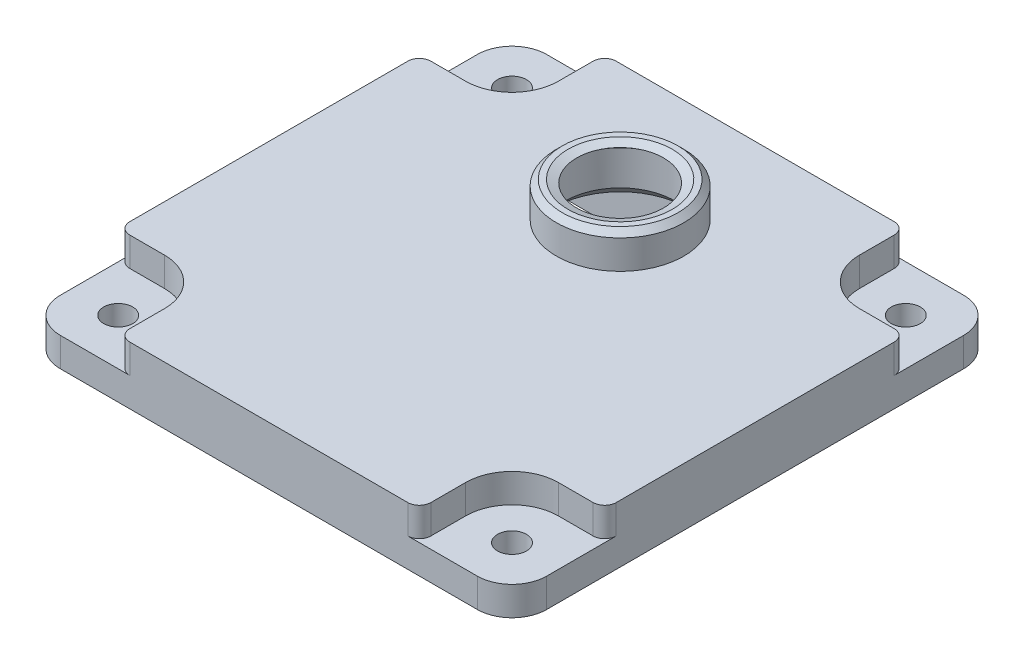
SolidWorks part; units mm, degrees
ref_plane "Front Plane" through (0, 0, 0) normal (0, 0, 1) x (1, 0, 0)
ref_plane "Top Plane" through (0, 0, 0) normal (0, 1, 0) x (1, 0, 0)
ref_plane "Right Plane" through (0, 0, 0) normal (1, 0, 0) x (0, 0, -1)
sketch "Sketch2" plane through (0, 0, 0) normal (0, 1, 0) x (1, 0, 0)
  line L1 (-21, 21) -> (21, 21)
  line L2 (-21, 21) -> (-21, -21)
  line L3 (-21, -21) -> (21, -21)
  line L4 (21, 21) -> (21, -21)
  line L5 (-21, 21) -> (21, -21) construction
  line L6 (-21, -21) -> (21, 21) construction
  circle A0 centre (0, 9.3373) radius 4.75
  point P0 (0, 0)
  point P8 (0, 6.2967)
  point P9 (0, 13.6485)
  point P10 (0.4735, 10.1128)
  point P11 (0, 10.3999)
  point P12 (0, 9.3373)
  dimension "D3" = 9.5
  dimension "D1" = 42
  dimension "D2" = 42
extrude "Boss-Extrude1" add sketch "Sketch2" against normal blind 2
ref_plane "Plane1" through (0, 0, -9.3373) normal (0, 0, 1) x (1, 0, 0)
sketch "Sketch3" plane through (0, 0, -9.3373) normal (0, 0, 1) x (1, 0, 0)
  line L1 (-4.75, 0) -> (-5.5, 0)
  line L2 (-5.5, 0) -> (-5.5, 3)
  line L4 (-5.5, 3) -> (-4.5, 3)
  line L8 (-4.75, 2) -> (-4.75, 0)
  line L9 (0, 0) -> (0, 7.3617) construction
  line L10 (-4.75, 2) -> (-3.75, 2.727)
  line L11 (-3.75, 2.727) -> (-4.5, 3)
  line L13 (0, 1.3621) -> (-4.5, 3) construction
  point P6 (-3.4803, 2.1355)
  point P8 (0, 0)
  point P13 (0, 0)
  point P14 (-3.6076, 2.6879)
  point P15 (-3.1722, 2.5167)
  point P16 (-3.7379, 2.7226)
  point P17 (-4.75, 1.7782)
  dimension "D1" = 70
  dimension "D2" = 3
  dimension "D3" = 1
  dimension "D4" = 0.75
  dimension "D5" = 0.75
  dimension "D6" = 2
revolve "Revolve1" add sketch "Sketch3" angle 360 about L9
sketch "Sketch4" plane through (0, -2, 0) normal (0, -1, 0) x (1, 0, 0)
  line L8 (-21, 21) -> (21, 21)
  line L9 (-21, 21) -> (-21, -21)
  line L10 (-21, -21) -> (21, -21)
  line L11 (21, 21) -> (21, -21)
  line L12 (-21, 21) -> (21, -21) construction
  line L13 (-21, -21) -> (21, 21) construction
  line L14 (-17, 11.5228) -> (-17, -11.5228)
  line L15 (-11.5228, -17) -> (11.5228, -17)
  line L16 (17, 11.5228) -> (17, -11.5228)
  line L17 (-11.5228, 17) -> (11.5228, 17)
  arc A12 (-16.5455, -12.0207) -> (-12.0207, -16.5455) centre (-17, -17) cw
  arc A13 (12.0207, -16.5455) -> (16.5455, -12.0207) centre (17, -17) cw
  arc A14 (16.5455, 12.0207) -> (12.0207, 16.5455) centre (17, 17) cw
  arc A15 (-12.0207, 16.5455) -> (-16.5455, 12.0207) centre (-17, 17) cw
  arc A16 (-16.5455, -12.0207) -> (-17, -11.5228) centre (-16.5, -11.5228) cw
  arc A17 (-12.0207, -16.5455) -> (-11.5228, -17) centre (-11.5228, -16.5) ccw
  arc A18 (12.0207, -16.5455) -> (11.5228, -17) centre (11.5228, -16.5) cw
  arc A19 (16.5455, -12.0207) -> (17, -11.5228) centre (16.5, -11.5228) ccw
  arc A20 (16.5455, 12.0207) -> (17, 11.5228) centre (16.5, 11.5228) cw
  arc A21 (12.0207, 16.5455) -> (11.5228, 17) centre (11.5228, 16.5) ccw
  arc A22 (-12.0207, 16.5455) -> (-11.5228, 17) centre (-11.5228, 16.5) cw
  arc A23 (-16.5455, 12.0207) -> (-17, 11.5228) centre (-16.5, 11.5228) ccw
  point P32 (0, 0)
  point P33 (0, 0)
extrude "Boss-Extrude2" add sketch "Sketch4" along normal blind 3
sketch "Sketch6" plane through (0, -2, 0) normal (0, -1, 0) x (1, 0, 0)
  line L8 (-16.5, 11.5228) -> (-16.5, -11.5228)
  line L9 (-11.5228, -16.5) -> (11.5228, -16.5)
  line L10 (16.5, -11.5228) -> (16.5, 11.5228)
  line L11 (11.5228, 16.5) -> (-11.5228, 16.5)
  line L12 (-16.5, 11.5228) -> (-16.5, -11.5228)
  line L13 (-11.5228, -16.5) -> (11.5228, -16.5)
  line L14 (16.5, -11.5228) -> (16.5, 11.5228)
  line L15 (11.5228, 16.5) -> (-11.5228, 16.5)
  line L16 (-17, 11.5228) -> (-17, -11.5228)
  line L17 (-11.5228, -17) -> (11.5228, -17)
  line L18 (17, -11.5228) -> (17, 11.5228)
  line L19 (11.5228, 17) -> (-11.5228, 17)
  line L20 (-17, 11.5228) -> (-17, -11.5228)
  line L21 (-11.5228, -17) -> (11.5228, -17)
  line L22 (17, -11.5228) -> (17, 11.5228)
  line L23 (11.5228, 17) -> (-11.5228, 17)
  arc A24 (-11.5228, -16.5) -> (-16.5, -11.5228) centre (-17, -17) ccw
  arc A25 (16.5, -11.5228) -> (11.5228, -16.5) centre (17, -17) ccw
  arc A26 (11.5228, 16.5) -> (16.5, 11.5228) centre (17, 17) ccw
  arc A27 (-16.5, 11.5228) -> (-11.5228, 16.5) centre (-17, 17) ccw
  arc A28 (-11.5228, -16.5) -> (-16.5, -11.5228) centre (-17, -17) ccw
  arc A29 (16.5, -11.5228) -> (11.5228, -16.5) centre (17, -17) ccw
  arc A30 (11.5228, 16.5) -> (16.5, 11.5228) centre (17, 17) ccw
  arc A31 (-16.5, 11.5228) -> (-11.5228, 16.5) centre (-17, 17) ccw
  arc A32 (-17, -11.5228) -> (-16.5455, -12.0207) centre (-16.5, -11.5228) ccw
  arc A33 (-12.0207, -16.5455) -> (-16.5455, -12.0207) centre (-17, -17) ccw
  arc A34 (-12.0207, -16.5455) -> (-11.5228, -17) centre (-11.5228, -16.5) ccw
  arc A35 (11.5228, -17) -> (12.0207, -16.5455) centre (11.5228, -16.5) ccw
  arc A36 (16.5455, -12.0207) -> (12.0207, -16.5455) centre (17, -17) ccw
  arc A37 (16.5455, -12.0207) -> (17, -11.5228) centre (16.5, -11.5228) ccw
  arc A38 (17, 11.5228) -> (16.5455, 12.0207) centre (16.5, 11.5228) ccw
  arc A39 (12.0207, 16.5455) -> (16.5455, 12.0207) centre (17, 17) ccw
  arc A40 (12.0207, 16.5455) -> (11.5228, 17) centre (11.5228, 16.5) ccw
  arc A41 (-11.5228, 17) -> (-12.0207, 16.5455) centre (-11.5228, 16.5) ccw
  arc A42 (-16.5455, 12.0207) -> (-12.0207, 16.5455) centre (-17, 17) ccw
  arc A43 (-16.5455, 12.0207) -> (-17, 11.5228) centre (-16.5, 11.5228) ccw
  arc A44 (-17, -11.5228) -> (-16.5455, -12.0207) centre (-16.5, -11.5228) ccw
  arc A45 (-12.0207, -16.5455) -> (-16.5455, -12.0207) centre (-17, -17) ccw
  arc A46 (-12.0207, -16.5455) -> (-11.5228, -17) centre (-11.5228, -16.5) ccw
  arc A47 (11.5228, -17) -> (12.0207, -16.5455) centre (11.5228, -16.5) ccw
  arc A48 (16.5455, -12.0207) -> (12.0207, -16.5455) centre (17, -17) ccw
  arc A49 (16.5455, -12.0207) -> (17, -11.5228) centre (16.5, -11.5228) ccw
  arc A50 (17, 11.5228) -> (16.5455, 12.0207) centre (16.5, 11.5228) ccw
  arc A51 (12.0207, 16.5455) -> (16.5455, 12.0207) centre (17, 17) ccw
  arc A52 (12.0207, 16.5455) -> (11.5228, 17) centre (11.5228, 16.5) ccw
  arc A53 (-11.5228, 17) -> (-12.0207, 16.5455) centre (-11.5228, 16.5) ccw
  arc A54 (-16.5455, 12.0207) -> (-12.0207, 16.5455) centre (-17, 17) ccw
  arc A55 (-16.5455, 12.0207) -> (-17, 11.5228) centre (-16.5, 11.5228) ccw
  dimension "D1" = 0.5
  dimension "D2" = 0
extrude "Boss-Extrude3" add sketch "Sketch6" along normal up to surface (3 mm away) up to face at (0, -5, 0)
sketch "Sketch7" plane through (0, -2, 0) normal (0, -1, 0) x (1, 0, 0)
  line L8 (10.6754, 15.5) -> (-10.6754, 15.5)
  line L9 (-15.5, 10.6754) -> (-15.5, -10.6754)
  line L10 (-10.6754, -15.5) -> (10.6754, -15.5)
  line L11 (15.5, -10.6754) -> (15.5, 10.6754)
  line L12 (10.6754, 15.5) -> (-10.6754, 15.5)
  line L13 (-15.5, 10.6754) -> (-15.5, -10.6754)
  line L14 (-10.6754, -15.5) -> (10.6754, -15.5)
  line L15 (15.5, -10.6754) -> (15.5, 10.6754)
  line L16 (11.5228, 16.5) -> (-11.5228, 16.5)
  line L17 (-16.5, 11.5228) -> (-16.5, -11.5228)
  line L18 (-11.5228, -16.5) -> (11.5228, -16.5)
  line L19 (16.5, -11.5228) -> (16.5, 11.5228)
  line L20 (11.5228, 16.5) -> (-11.5228, 16.5)
  line L21 (-16.5, 11.5228) -> (-16.5, -11.5228)
  line L22 (-11.5228, -16.5) -> (11.5228, -16.5)
  line L23 (16.5, -11.5228) -> (16.5, 11.5228)
  arc A8 (10.6754, 15.5) -> (15.5, 10.6754) centre (17, 17) ccw
  arc A9 (-15.5, 10.6754) -> (-10.6754, 15.5) centre (-17, 17) ccw
  arc A10 (-10.6754, -15.5) -> (-15.5, -10.6754) centre (-17, -17) ccw
  arc A11 (15.5, -10.6754) -> (10.6754, -15.5) centre (17, -17) ccw
  arc A12 (10.6754, 15.5) -> (15.5, 10.6754) centre (17, 17) ccw
  arc A13 (-15.5, 10.6754) -> (-10.6754, 15.5) centre (-17, 17) ccw
  arc A14 (-10.6754, -15.5) -> (-15.5, -10.6754) centre (-17, -17) ccw
  arc A15 (15.5, -10.6754) -> (10.6754, -15.5) centre (17, -17) ccw
  arc A16 (11.5228, 16.5) -> (16.5, 11.5228) centre (17, 17) ccw
  arc A17 (-16.5, 11.5228) -> (-11.5228, 16.5) centre (-17, 17) ccw
  arc A18 (-11.5228, -16.5) -> (-16.5, -11.5228) centre (-17, -17) ccw
  arc A19 (16.5, -11.5228) -> (11.5228, -16.5) centre (17, -17) ccw
  arc A20 (11.5228, 16.5) -> (16.5, 11.5228) centre (17, 17) ccw
  arc A21 (-16.5, 11.5228) -> (-11.5228, 16.5) centre (-17, 17) ccw
  arc A22 (-11.5228, -16.5) -> (-16.5, -11.5228) centre (-17, -17) ccw
  arc A23 (16.5, -11.5228) -> (11.5228, -16.5) centre (17, -17) ccw
  dimension "D1" = 1
  dimension "D2" = 0
extrude "Boss-Extrude5" add sketch "Sketch7" along normal blind 5
sketch "Sketch9" plane through (0, 0, 0) normal (0, 1, 0) x (1, 0, 0)
  circle A0 centre (-17, 17) radius 1.25
  circle A1 centre (17, 17) radius 1.25
  circle A2 centre (-17, -17) radius 1.25
  circle A3 centre (17, -17) radius 1.25
  dimension "D1" = 2.5
sketch "Sketch8" plane through (0, 0, 0) normal (0, 1, 0) x (1, 0, 0)
  line L0 (-17, 13) -> (-21, 13)
  line L1 (-21, -21) -> (-21, 21) construction
  line L2 (-21, 13) -> (-21, 21)
  line L3 (-13, 17) -> (-13, 21)
  line L4 (-21, 21) -> (21, 21) construction
  line L5 (-13, 21) -> (-21, 21)
  line L6 (13, 17) -> (13, 21)
  line L7 (13, 21) -> (21, 21)
  line L8 (21, 21) -> (21, 13)
  line L9 (17, 13) -> (21, 13)
  line L10 (21, -21) -> (21, 21) construction
  line L11 (-21, -17) -> (-21, -21)
  line L12 (-21, -21) -> (-17, -21)
  line L13 (-21, -21) -> (21, -21) construction
  line L14 (-13, -17) -> (-13, -21)
  line L15 (-13, -21) -> (-17, -21)
  line L16 (-17, -13) -> (-21, -13)
  line L17 (-21, -13) -> (-21, -17)
  line L18 (17, -13) -> (21, -13)
  line L19 (21, -13) -> (21, -21)
  line L20 (21, -21) -> (17, -21)
  line L21 (13, -17) -> (13, -21)
  line L22 (13, -21) -> (17, -21)
  arc A0 (-17, 13) -> (-13, 17) centre (-17, 17) ccw
  arc A2 (13, 17) -> (17, 13) centre (17, 17) ccw
  arc A3 (17, -13) -> (13, -17) centre (17, -17) ccw
  arc A4 (-13, -17) -> (-17, -13) centre (-17, -17) ccw
  point P1 (-17, 13)
extrude "Cut-Extrude1" cut sketch "Sketch8" against normal blind 2.5
extrude "Cut-Extrude2" cut sketch "Sketch9" against normal through all
fillet "Fillet1" radius 3 4 edges at (21, -3.75, 21) (-21, -3.75, 21) (21, -3.75, -21) (-21, -3.75, -21)
fillet "Fillet2" radius 1 8 edges at (-21, -1.25, -13) (-13, -1.25, -21) (13, -1.25, -21) (21, -1.25, -13) (21, -1.25, 13) (13, -1.25, 21) (-13, -1.25, 21) (-21, -1.25, 13)
chamfer "Chamfer1" distance 1 angle 45 1 edges at (0, -2, -4.5873)
chamfer "Chamfer2" distance 0.5 angle 45 1 edges at (0, 3, -14.8373)
